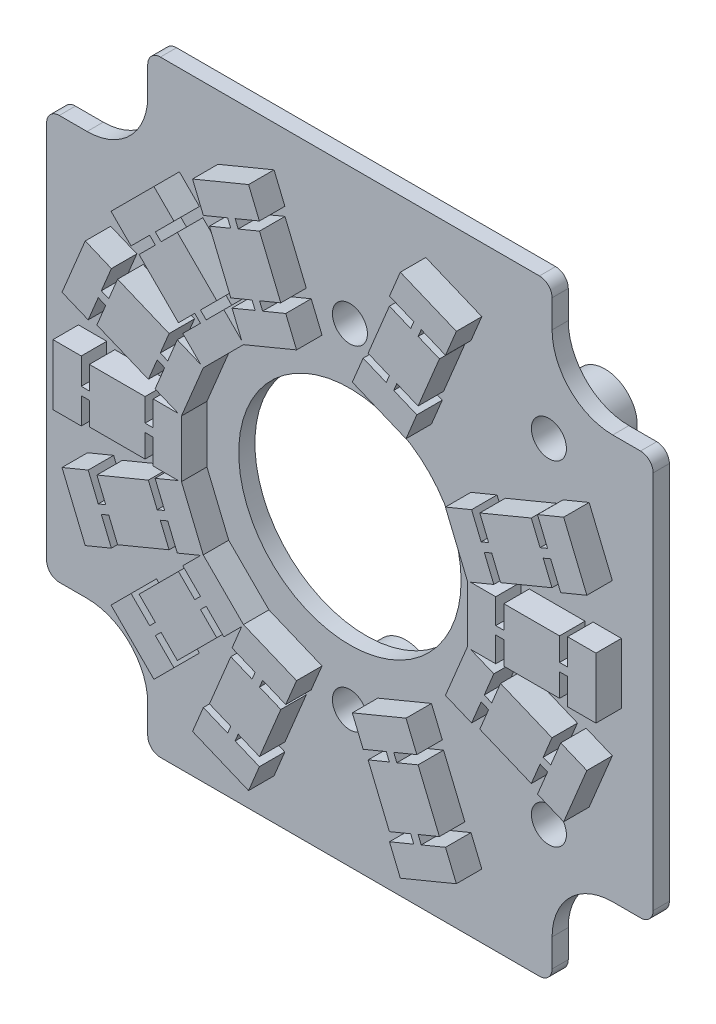
SolidWorks part; units mm, degrees
ref_plane "Front Plane" through (0, 0, 0) normal (0, 0, 1) x (1, 0, 0)
ref_plane "Top Plane" through (0, 0, 0) normal (0, 1, 0) x (1, 0, 0)
ref_plane "Right Plane" through (0, 0, 0) normal (1, 0, 0) x (0, 0, -1)
sketch "Sketch3" plane through (0, 0, 0) normal (0, 0, 1) x (1, 0, 0)
  line L4 (-20.8352, -12.6031) -> (-19.0889, -12.6031)
  line L5 (16.4711, -11.8094) -> (16.4711, 12.0031)
  line L6 (15.6773, 12.7969) -> (13.9311, 12.7969)
  line L7 (-21.6289, 12.0031) -> (-21.6289, -11.8094)
  line L8 (-14.4852, -18.9531) -> (9.3273, -18.9531)
  line L9 (10.1211, -18.1594) -> (10.1211, -16.4131)
  line L10 (9.3273, 19.1469) -> (-14.4852, 19.1469)
  line L11 (-15.2789, 18.3531) -> (-15.2789, 16.6069)
  line L12 (1.8761, -31.0605) -> (-0.0593, -31.0605)
  line L13 (12.8381, -31.0605) -> (1.8761, -31.0605)
  line L14 (13.7967, -31.0605) -> (12.8381, -31.0605)
  line L15 (15.8583, -34.0759) -> (15.8583, -33.1222)
  line L16 (15.8583, -53.8097) -> (15.8583, -34.0759)
  line L17 (15.8583, -54.7695) -> (15.8583, -53.8097)
  line L18 (12.8508, -56.8311) -> (13.7967, -56.8311)
  line L19 (-0.0465, -56.8311) -> (1.8634, -56.8311)
  line L20 (1.8634, -56.8311) -> (12.8508, -56.8311)
  line L21 (-6.6776, -56.8311) -> (-0.0465, -56.8311)
  line L22 (-8.7392, -33.1222) -> (-8.7392, -54.7695)
  line L23 (-0.0593, -31.0605) -> (-6.6776, -31.0605)
  line L24 (-21.6289, 0.0969) -> (16.4711, 0.0969) construction
  line L25 (-2.5789, 19.1469) -> (-2.5789, -18.9531) construction
  line L26 (-2.5789, -10.4031) -> (9.9211, -10.4031) construction
  line L27 (9.9211, -10.4031) -> (9.9211, 10.5969) construction
  line L28 (9.9211, 10.5969) -> (-2.5789, 10.5969) construction
  line L29 (-2.5789, 10.5969) -> (-2.5789, -10.4031) construction
  line L30 (-15.2789, -16.4131) -> (-15.2789, -18.1594)
  line L31 (13.9311, -12.6031) -> (15.6773, -12.6031)
  line L32 (10.1211, 16.6069) -> (10.1211, 18.3531)
  line L33 (-19.0889, 12.7969) -> (-20.8352, 12.7969)
  line L40 (1.6413, -4.0348) -> (1.6413, 4.2118) construction
  line L41 (-6.6053, -4.0348) -> (1.6413, -4.0348) construction
  line L42 (-6.6053, 4.2118) -> (-6.6053, -4.0348) construction
  line L43 (1.6413, 4.2118) -> (-6.6053, 4.2118) construction
  circle A1 centre (-2.5789, -10.4031) radius 1.1 construction
  circle A2 centre (9.9211, -10.4031) radius 1.1 construction
  circle A3 centre (-2.5789, 10.5969) radius 1.1 construction
  circle A4 centre (9.9211, 10.5969) radius 1.1 construction
  circle A5 centre (-2.5789, -10.4031) radius 1.1
  circle A6 centre (9.9211, -10.4031) radius 1.1
  circle A7 centre (-2.5789, 10.5969) radius 1.1
  arc A12 (15.8583, -33.1222) -> (13.7967, -31.0605) centre (13.7967, -33.1222) ccw
  arc A13 (13.7967, -56.8311) -> (15.8583, -54.7695) centre (13.7967, -54.7695) ccw
  arc A14 (-8.7392, -54.7695) -> (-6.6776, -56.8311) centre (-6.6776, -54.7695) ccw
  arc A15 (-6.6776, -31.0605) -> (-8.7392, -33.1222) centre (-6.6776, -33.1222) ccw
  circle A16 centre (9.9211, 10.5969) radius 1.1
  arc A18 (10.1211, -16.4131) -> (13.9311, -12.6031) centre (13.9311, -16.4131) cw
  arc A19 (13.9311, 12.7969) -> (10.1211, 16.6069) centre (13.9311, 16.6069) cw
  arc A20 (-15.2789, 16.6069) -> (-19.0889, 12.7969) centre (-19.0889, 16.6069) cw
  circle A21 centre (-2.5789, 0.0969) radius 3.2986 construction
  circle A26 centre (-2.5789, 0.0969) radius 6.985
  arc A27 (-19.0889, -12.6031) -> (-15.2789, -16.4131) centre (-19.0889, -16.4131) cw
  arc A28 (-20.8352, -12.6031) -> (-21.6289, -11.8094) centre (-20.8352, -11.8094) cw
  arc A29 (-21.6289, 12.0031) -> (-20.8352, 12.7969) centre (-20.8352, 12.0031) cw
  arc A30 (-15.2789, 18.3531) -> (-14.4852, 19.1469) centre (-14.4852, 18.3531) cw
  arc A31 (9.3273, 19.1469) -> (10.1211, 18.3531) centre (9.3273, 18.3531) cw
  arc A32 (15.6773, 12.7969) -> (16.4711, 12.0031) centre (15.6773, 12.0031) cw
  arc A33 (16.4711, -11.8094) -> (15.6773, -12.6031) centre (15.6773, -11.8094) cw
  arc A34 (9.3273, -18.9531) -> (10.1211, -18.1594) centre (9.3273, -18.1594) ccw
  arc A35 (-14.4852, -18.9531) -> (-15.2789, -18.1594) centre (-14.4852, -18.1594) cw
  point P3 (-2.5789, 0.0969)
  point P5 (-2.5789, 0.0969)
  point P7 (-2.5789, 0.0969)
  point P70 (-21.6289, 12.7969)
  point P73 (-15.2789, 19.1469)
  point P78 (16.4711, 12.7969)
  point P81 (16.4711, -12.6031)
  point P84 (10.1211, -18.9531)
  point P87 (-15.2789, -18.9531)
  dimension "D1" = 38.1
  dimension "D7" = 13.97
  dimension "D8" = 3.81
  dimension "D9" = 0.7937
  dimension "D2" = 38.1
  dimension "D3" = 25.4
  dimension "D4" = 25.4
  dimension "D5" = 8.2466
  dimension "D6" = 8.2466
extrude "Boss-Extrude1" add sketch "Sketch3" along normal blind 1.016 contours A15 L23 L12 L13 L14 A12 L15 L16 L17 A13 L18 L20 L19 L21 A14 L22 | L11 L33 L7 L4 L30 L8 L9 L31 L5 L6 L32 L10 A26 A16 A7 A6 A5 region at (-21.0154, -11.9897, 0)
sketch "Sketch4" plane through (0, 0, 0) normal (0, 0, 1) x (1, 0, 0)
  line L1 (-17.5075, 8.1205) -> (-14.2739, 6.7812)
  line L2 (-19.4416, -1.6031) -> (-15.9416, -1.6031)
  line L3 (-19.4416, -1.6031) -> (-19.4416, 1.7969)
  line L4 (-19.4416, 1.7969) -> (-15.9416, 1.7969)
  line L5 (-15.9416, -1.6031) -> (-15.9416, 1.7969)
  line L6 (-19.4416, -1.6031) -> (-15.9416, 1.7969) construction
  line L7 (-19.4416, 1.7969) -> (-15.9416, -1.6031) construction
  line L8 (-18.8086, 4.9794) -> (-17.5075, 8.1205)
  line L9 (-18.8086, 4.9794) -> (-15.575, 3.64)
  line L10 (-15.575, 3.64) -> (-14.2739, 6.7812)
  line L11 (-13.3006, 13.2227) -> (-10.8257, 10.7478)
  line L12 (-15.7047, 10.8185) -> (-13.3006, 13.2227)
  line L13 (-15.7047, 10.8185) -> (-13.2299, 8.3437)
  line L14 (-13.2299, 8.3437) -> (-10.8257, 10.7478)
  line L15 (-7.4614, 16.3266) -> (-6.122, 13.093)
  line L16 (-10.6026, 15.0254) -> (-7.4614, 16.3266)
  line L17 (-10.6026, 15.0254) -> (-9.2632, 11.7918)
  line L18 (-9.2632, 11.7918) -> (-6.122, 13.093)
  line L19 (-0.8789, 16.9596) -> (-0.8789, 13.4596) [skipped]
  line L20 (-4.2789, 16.9596) -> (-0.8789, 16.9596) [skipped]
  line L21 (-4.2789, 16.9596) -> (-4.2789, 13.4596) [skipped]
  line L22 (-4.2789, 13.4596) -> (-0.8789, 13.4596) [skipped]
  line L23 (5.4448, 15.0254) -> (4.1054, 11.7918)
  line L24 (2.3036, 16.3266) -> (5.4448, 15.0254)
  line L25 (2.3036, 16.3266) -> (0.9642, 13.093)
  line L26 (0.9642, 13.093) -> (4.1054, 11.7918)
  line L27 (10.5469, 10.8185) -> (8.072, 8.3437) [skipped]
  line L28 (8.1428, 13.2227) -> (10.5469, 10.8185) [skipped]
  line L29 (8.1428, 13.2227) -> (5.6679, 10.7478) [skipped]
  line L30 (5.6679, 10.7478) -> (8.072, 8.3437) [skipped]
  line L31 (13.6508, 4.9794) -> (10.4172, 3.64)
  line L32 (12.3497, 8.1205) -> (13.6508, 4.9794)
  line L33 (12.3497, 8.1205) -> (9.1161, 6.7812)
  line L34 (9.1161, 6.7812) -> (10.4172, 3.64)
  line L35 (14.2838, -1.6031) -> (10.7838, -1.6031)
  line L36 (14.2838, 1.7969) -> (14.2838, -1.6031)
  line L37 (14.2838, 1.7969) -> (10.7838, 1.7969)
  line L38 (10.7838, 1.7969) -> (10.7838, -1.6031)
  line L39 (12.3497, -7.9268) -> (9.1161, -6.5874)
  line L40 (13.6508, -4.7856) -> (12.3497, -7.9268)
  line L41 (13.6508, -4.7856) -> (10.4172, -3.4462)
  line L42 (10.4172, -3.4462) -> (9.1161, -6.5874)
  line L43 (8.1428, -13.029) -> (5.6679, -10.5541) [skipped]
  line L44 (10.5469, -10.6248) -> (8.1428, -13.029) [skipped]
  line L45 (10.5469, -10.6248) -> (8.072, -8.1499) [skipped]
  line L46 (8.072, -8.1499) -> (5.6679, -10.5541) [skipped]
  line L47 (2.3036, -16.1328) -> (0.9642, -12.8992)
  line L48 (5.4448, -14.8317) -> (2.3036, -16.1328)
  line L49 (5.4448, -14.8317) -> (4.1054, -11.5981)
  line L50 (4.1054, -11.5981) -> (0.9642, -12.8992)
  line L51 (-4.2789, -16.7659) -> (-4.2789, -13.2659) [skipped]
  line L52 (-0.8789, -16.7659) -> (-4.2789, -16.7659) [skipped]
  line L53 (-0.8789, -16.7659) -> (-0.8789, -13.2659) [skipped]
  line L54 (-0.8789, -13.2659) -> (-4.2789, -13.2659) [skipped]
  line L55 (-10.6026, -14.8317) -> (-9.2632, -11.5981)
  line L56 (-7.4614, -16.1328) -> (-10.6026, -14.8317)
  line L57 (-7.4614, -16.1328) -> (-6.122, -12.8992)
  line L58 (-6.122, -12.8992) -> (-9.2632, -11.5981)
  line L59 (-15.7047, -10.6248) -> (-13.2299, -8.1499)
  line L60 (-13.3006, -13.029) -> (-15.7047, -10.6248)
  line L61 (-13.3006, -13.029) -> (-10.8257, -10.5541)
  line L62 (-10.8257, -10.5541) -> (-13.2299, -8.1499)
  line L63 (-18.8086, -4.7856) -> (-15.575, -3.4462)
  line L64 (-17.5075, -7.9268) -> (-18.8086, -4.7856)
  line L65 (-17.5075, -7.9268) -> (-14.2739, -6.5874)
  line L66 (-14.2739, -6.5874) -> (-15.575, -3.4462)
  line L67 (-2.5789, 0.0969) -> (-15.9416, 1.7969) construction
  line L68 (-2.5789, 0.0969) -> (-14.2739, 6.7812) construction
  point P7 (-17.6916, 0.0969)
  dimension "D1" = 3.5
  dimension "D2" = 3.4
  dimension "D4" = 22.5
  dimension "D3" = 16
sketch "Sketch5" plane through (-0.0742, 0.0026, -3.44) normal (0, 0, 1) x (1, 0, 0)
  circle A0 centre (-2.5047, 10.5942) radius 1.1
  circle A1 centre (9.9953, 10.5942) radius 1.1
  circle A2 centre (9.9953, -10.4058) radius 1.1
  circle A3 centre (-2.5047, -10.4058) radius 1.1
  circle A4 centre (-2.5047, -10.4058) radius 2.032
  circle A5 centre (9.9953, -10.4058) radius 2.032
  circle A6 centre (-2.5047, 10.5942) radius 2.032
  circle A7 centre (9.9953, 10.5942) radius 2.032
  dimension "D1" = 4.064
  dimension "D2" = 4.064
  dimension "D3" = 4.064
  dimension "D4" = 4.064
extrude "Boss-Extrude3" add sketch "Sketch5" against normal blind 2.5 from surface contours A6 A0 | A7 A1 | A5 A2 | A4 A3 region at (-4.5534, -10.4031, -3.44) region at (7.9466, -10.4031, -3.44) region at (-4.5534, 10.5969, -3.44) region at (7.9466, 10.5969, -3.44) starting at face at (-2.5789, 0.0969, 0)
sketch "Sketch9" plane through (0, 0, 0) normal (0, 0, 1) x (1, 0, 0)
  line L0 (-9.5639, 0.0969) -> (-21.6289, 0.0969) construction
  line L1 (-21.4402, 0.0969) -> (-20.9322, 0.0969) construction
  line L2 (-17.3464, -1.6031) -> (-13.8464, -1.6031)
  line L3 (-17.3464, -1.6031) -> (-17.3464, -0.1571)
  line L4 (-17.3464, 1.7969) -> (-13.8464, 1.7969)
  line L5 (-13.8464, -1.6031) -> (-13.8464, -0.1571)
  line L6 (-17.3464, -1.6031) -> (-13.8464, 1.7969) construction
  line L7 (-17.3464, 1.7969) -> (-13.8464, -1.6031) construction
  line L8 (-13.3384, -1.7278) -> (-11.5604, -1.7278)
  line L9 (-13.3384, -1.7278) -> (-13.3384, -0.1571)
  line L10 (-13.3384, 1.9215) -> (-11.5604, 1.9215)
  line L11 (-11.5604, -1.7278) -> (-11.5604, 1.9215)
  line L12 (-13.3384, -1.7278) -> (-11.5604, 1.9215) construction
  line L13 (-13.3384, 1.9215) -> (-11.5604, -1.7278) construction
  line L14 (-19.6324, -1.8081) -> (-17.8544, -1.8081)
  line L15 (-19.6324, -1.8081) -> (-19.6324, 2.0019)
  line L16 (-19.6324, 2.0019) -> (-17.8544, 2.0019)
  line L17 (-17.8544, -1.8081) -> (-17.8544, -0.1571)
  line L18 (-19.6324, -1.8081) -> (-17.8544, 2.0019) construction
  line L19 (-19.6324, 2.0019) -> (-17.8544, -1.8081) construction
  line L20 (-21.4402, 0.0969) -> (-20.9322, 0.0969) construction
  line L21 (-21.6289, 12.0031) -> (-21.6289, -11.8094) construction
  line L22 (-17.8544, 0.3509) -> (-17.3464, 0.3509)
  line L23 (-17.8544, -0.1571) -> (-17.3464, -0.1571)
  line L24 (-17.4322, 0.0969) -> (-16.9242, 0.0969) construction
  line L26 (-13.8464, -0.1571) -> (-13.3384, -0.1571)
  line L27 (-13.8464, 0.3509) -> (-13.3384, 0.3509)
  line L28 (-17.8544, 0.3509) -> (-17.8544, 2.0019)
  line L29 (-17.3464, 0.3509) -> (-17.3464, 1.7969)
  line L30 (-13.8464, 0.3509) -> (-13.8464, 1.7969)
  line L31 (-13.3384, 0.3509) -> (-13.3384, 1.9215)
  circle A2 centre (-2.5789, 0.0969) radius 6.985 construction
  point P7 (-15.5964, 0.0969)
  point P12 (-12.4494, 0.0969)
  point P17 (-18.7434, 0.0969)
  dimension "D1" = 1.778
  dimension "D2" = 3.5
  dimension "D3" = 3.4
  dimension "D4" = 3.81
  dimension "D5" = 0.508
  dimension "D6" = 0.508
  dimension "D7" = 0.508
  dimension "D8" = 0.508
extrude "Boss-Extrude4" add sketch "Sketch9" along normal blind 1.6 from surface contours L14 L17 L16 L15 | L2 L5 L4 L3 | L8 L11 L10 L9 region at (-15.6314, 0.0969, 0) starting at face at (-2.5789, 0.0969, 1.016)
pattern_circular "CirPattern1" count 16 over 360 about axis through (-2.5789, 0.0969, 1.016) along (0, 0, 1) skipping 4, 6, 10, 12 of "Boss-Extrude4"
